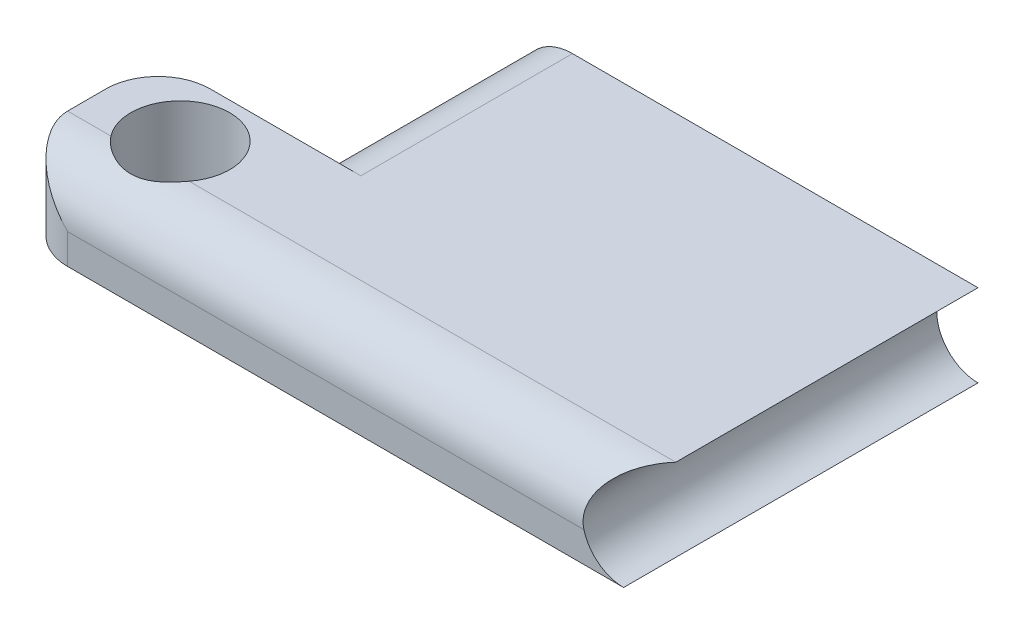
SolidWorks part; units mm, degrees
ref_plane "Front Plane" through (0, 0, 0) normal (0, 0, 1) x (1, 0, 0)
ref_plane "Top Plane" through (0, 0, 0) normal (0, 1, 0) x (1, 0, 0)
ref_plane "Right Plane" through (0, 0, 0) normal (1, 0, 0) x (0, 0, -1)
sketch "Sketch1" plane through (0, 0, 0) normal (0, 0, 1) x (1, 0, 0)
  line L0 (0, 150) -> (0, 0)
  line L1 (0, 150) -> (1106.9725, 150)
  line L3 (0, 0) -> (1106.9725, 0)
  line L4 (1106.9725, 150) -> (1106.9725, 0)
extrude "Boss-Extrude1" add sketch "Sketch1" along normal blind 645 contours L1 L4 L3 L0
sketch "Sketch2" plane through (0, 0, 0) normal (0, -1, 0) x (1, 0, 0)
  line L0 (0, 645) -> (0, 0) construction
  line L1 (0, 645) -> (1106.9725, 645) construction
  circle A0 centre (150, 495) radius 90
  dimension "D1" = 180
  dimension "D2" = 150
  dimension "D3" = 150
extrude "Cut-Extrude1" cut sketch "Sketch2" against normal through all contours A0
sketch "Sketch3" plane through (0, 0, 0) normal (0, -1, 0) x (1, 0, 0)
  line L1 (0, 0) -> (273.9363, 0)
  line L2 (0, 0) -> (0, 385.2587)
  line L3 (0, 385.2587) -> (273.9363, 385.2587)
  line L4 (273.9363, 0) -> (273.9363, 385.2587)
extrude "Cut-Extrude2" cut sketch "Sketch3" against normal through all
sketch "Sketch4" plane through (0, 0, 645) normal (0, 0, 1) x (1, 0, 0)
  line L0 (1106.9725, 150) -> (1106.9725, 0) construction
  line L1 (1106.9725, 150) -> (1106.9725, 0)
  arc A0 (1106.9725, 0) -> (1106.9725, 150) centre (1106.9725, 75) cw
  dimension "D1" = 75
extrude "Cut-Extrude3" cut sketch "Sketch4" against normal through all contours L1 A0
fillet "Fillet1" radius 95 3 edges at (553.4863, 150, 645) (0, 75, 645) (0, 75, 385.2587)
fillet "Fillet2" radius 95 1 edges at (273.9363, 150, 192.6294)
